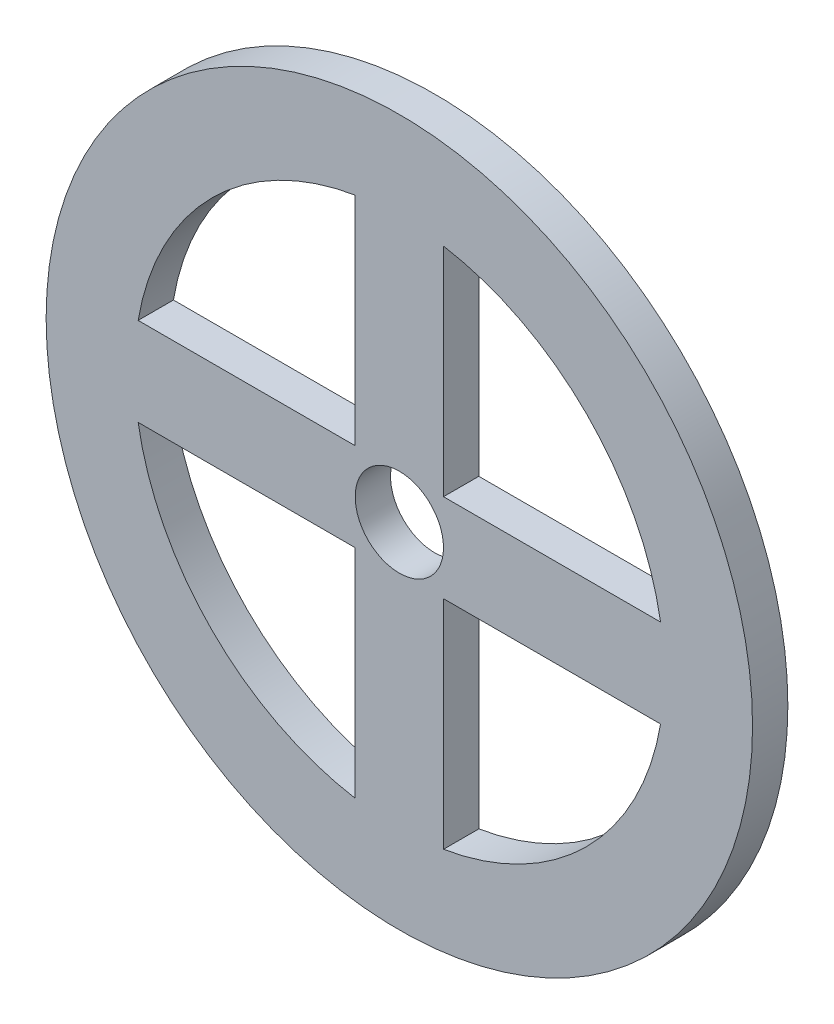
SolidWorks part; units mm, degrees
ref_plane "Front Plane" through (0, 0, 0) normal (0, 0, 1) x (1, 0, 0)
ref_plane "Top Plane" through (0, 0, 0) normal (0, 1, 0) x (1, 0, 0)
ref_plane "Right Plane" through (0, 0, 0) normal (1, 0, 0) x (0, 0, -1)
sketch "Sketch1" plane through (0, 0, 0) normal (0, 0, 1) x (1, 0, 0)
  line L0 (-3.175, 0) -> (-3.175, 18.7836)
  line L1 (3.175, 0) -> (3.175, 18.7836)
  line L2 (-3.175, 0) -> (-3.175, -18.7836)
  line L3 (3.175, 0) -> (3.175, -18.7836)
  line L4 (0, 3.175) -> (18.7836, 3.175)
  line L5 (0, -3.175) -> (18.7836, -3.175)
  line L6 (0, 3.175) -> (-18.7836, 3.175)
  line L7 (0, -3.175) -> (-18.7836, -3.175)
  circle A0 centre (0, 0) radius 25.4
  circle A1 centre (0, 0) radius 19.05
  circle A2 centre (0, 0) radius 3.175
  dimension "D1" = 50.8
  dimension "D2" = 38.1
  dimension "D3" = 6.35
extrude "Boss-Extrude1" add sketch "Sketch1" along normal blind 2.54 contours A0
extrude "Cut-Extrude2" cut sketch "Sketch1<4>" along normal blind 2.54 contours L7 A1 L2 | L0 A1 L6 | L4 A1 L1 | L3 A1 L5 | A2 region at (-9.4695, 9.4695, 0) region at (-9.4695, -9.4695, 0) region at (9.4695, 9.4695, 0) region at (9.4695, -9.4695, 0)
sketch "Sketch1<4>" plane through (0, 0, 0) normal (0, 0, 1) x (1, 0, 0) same geometry as "Sketch1"
